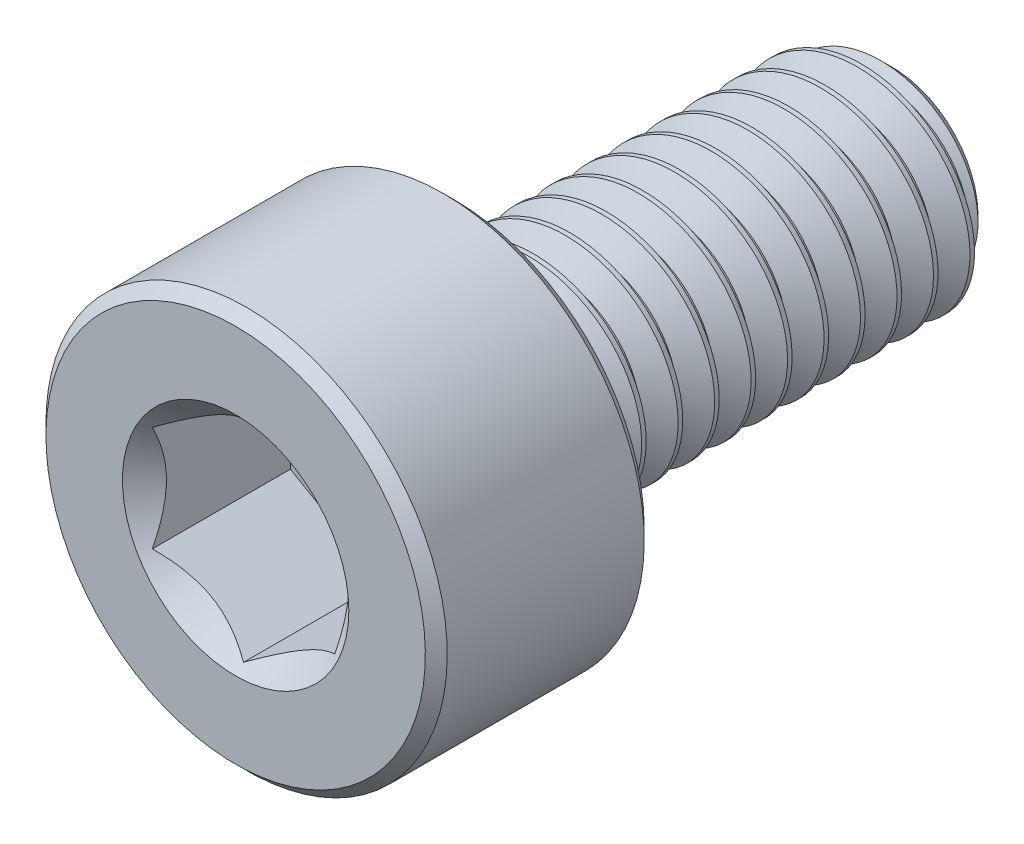
SolidWorks part; units mm, degrees
ref_plane "Front Plane" through (0, 0, 0) normal (0, 0, 1) x (1, 0, 0)
ref_plane "Top Plane" through (0, 0, 0) normal (0, 1, 0) x (1, 0, 0)
ref_plane "Right Plane" through (0, 0, 0) normal (1, 0, 0) x (0, 0, -1)
sketch "Sketch1" plane through (0, 0, 0) normal (1, 0, 0) x (0, 0, -1)
  line L0 (-4.5, 0) -> (4.5, 0) construction
  line L1 (4.5, 0) -> (4.5, 1.1752) construction
  line L2 (4.5, 1.1752) -> (4.1752, 1.5) construction
  line L3 (4.1752, 1.5) -> (4.125, 1.5) construction
  line L4 (4.125, 1.5) -> (-1.5, 1.5) construction
  line L5 (-1.5, 1.5) -> (-1.5, 2.75) construction
  line L6 (-1.5, 2.75) -> (-4.5, 2.75) construction
  line L7 (-4.5, 2.75) -> (-4.5, 0) construction
  line L8 (4.5, 1.1752) -> (4.5, 1.5) construction
  line L9 (4.4687, 1.5541) -> (4.7187, 1.1211) construction
  line L10 (4.7187, 1.1211) -> (4.9687, 1.5541) construction
  line L11 (4.9687, 1.5541) -> (4.4687, 1.5541) construction
  line L12 (4.7187, 1.5541) -> (4.7188, 1.5) construction
  line L13 (4.7187, 1.1211) -> (4.7187, 1.1752) construction
  line L14 (4.6875, 1.1752) -> (4.75, 1.1752) construction
  line L15 (4.5, 1.5) -> (4.9375, 1.5) construction
  line L16 (4.4844, 1.5271) -> (4.9531, 1.5271) construction
  line L17 (4.5, 0) -> (4.5, -1.5) construction
  line L18 (-1.65, 2.75) -> (-1.5, 2.6) construction
  line L19 (-4.35, 2.75) -> (-4.5, 2.6) construction
  line L20 (-1.5, 1.5) -> (-1.5, 0) construction
  line L21 (-1.5, 0.75) -> (0.5, 0.75) construction
  line L22 (0.5, 0.75) -> (2.5, 0.75) construction
  line L23 (2.5, 0.75) -> (4.5, 0.75) construction
  line L24 (0.5, 0.75) -> (0.5, 1.5) construction
  line L25 (0.5, 1.5) -> (0.5, 2.75) construction
  line L26 (2.5, 0.75) -> (2.5, 2.75) construction
  point P0 (-4.5, 1.25)
  point P3 (3.25, 1.5)
  point P4 (0, 0)
  point P18 (2.5, 1.5)
  point P22 (4.7187, 1.1752)
  point P24 (4.125, 1.5)
  point P25 (4.7188, 1.5)
  point P28 (4.7188, 1.5271)
  point P29 (3.25, -1.5)
  point P30 (0.5, 1.5)
  point P31 (-3, 2.75)
  point P37 (-2.025, 2.75)
  point P38 (-4.275, 2.75)
  point P45 (0.5, 0.75)
  point P46 (2.5, 0.75)
  dimension "D2" = 0.0625
  dimension "D7" = 0.15
  dimension "D8" = 0.15
  dimension "D9" = 0.15
  dimension "D10" = 0.075
  dimension "D11" = 0.375
  dimension "Drive Size" = 2.5
  dimension "Head Diameter" = 5.5
  dimension "Head Height" = 3
  dimension "Thread Pitch" = 0.5
  dimension "Thread Dia" = 3
  dimension "Length" = 6
  dimension "D12" = 0.375
  dimension "D4" = 1.25
  dimension "D3" = 45
sketch "Sketch2" plane through (0, 0, 0) normal (1, 0, 0) x (0, 0, -1)
  line L0 (-4.5, 0) -> (-4.5, 2.6)
  line L1 (-4.35, 2.75) -> (-1.65, 2.75)
  line L2 (-1.5, 2.6) -> (-1.5, 1.65)
  line L4 (4.1752, 1.5) -> (4.5, 1.1752)
  line L5 (4.5, 1.1752) -> (4.5, 0)
  line L6 (-1.5, 2.75) -> (-4.5, 2.75) construction
  line L7 (4.5, 0) -> (-4.5, 0)
  line L8 (-4.35, 2.75) -> (-4.5, 2.6) construction
  line L10 (-4.35, 2.75) -> (-4.5, 2.6)
  line L14 (-1.65, 2.75) -> (-1.5, 2.6) construction
  line L16 (-1.65, 2.75) -> (-1.5, 2.6)
  line L17 (-1.5, 1.5) -> (-1.5, 2.75) construction
  line L19 (-1.35, 1.5) -> (4.1752, 1.5)
  line L20 (4.125, 1.5) -> (-1.5, 1.5) construction
  arc A1 (-1.5, 1.65) -> (-1.35, 1.5) centre (-1.35, 1.65) ccw
  dimension "D3" = 0.15
revolve "Revolve1" add sketch "Sketch2" angle 360 about L7
sketch "Sketch3" plane through (0, 0, 4.5) normal (0, 0, 1) x (1, 0, 0)
  line L1 (1.25, -0.7217) -> (1.25, 0.7217)
  line L2 (1.25, 0.7217) -> (0, 1.4434)
  line L3 (0, 1.4434) -> (-1.25, 0.7217)
  line L4 (-1.25, 0.7217) -> (-1.25, -0.7217)
  line L5 (-1.25, -0.7217) -> (0, -1.4434)
  line L6 (0, -1.4434) -> (1.25, -0.7217)
  circle A0 centre (0, 0) radius 1.25 construction
  circle A1 centre (0, 0) radius 2.75 construction
  circle A2 centre (0, 0) radius 2.75 construction
  circle A3 centre (0, 0) radius 1.4434 construction
  point P13 (0, 0)
  dimension "D1" = 2.8868
extrude "Cut-Extrude1" cut sketch "Sketch3" against normal offset from surface (2 mm away) 1 up to face at (0, 2.6, 1.5)
sketch "Sketch4" plane through (0, 0, 4.5) normal (0, 0, 1) x (1, 0, 0)
  circle A0 centre (0, 0) radius 1.5516
  dimension "D1" = 3.1033
extrude "Cut-Extrude2" cut sketch "Sketch4" against normal up to vertex (1.5 mm away) draft 45 up to point (0, 2.75, 3)
sketch "Sketch11" plane through (0, 0, 0) normal (1, 0, 0) x (0, 0, -1)
  line L0 (-4.5, 0) -> (4.5, 0) construction
  line L1 (-4.5, 0) -> (4.5, 0) construction
  line L2 (-0.375, 0) -> (-0.375, 1.5) construction
  line L3 (4.125, 1.5) -> (-1.5, 1.5) construction
  line L4 (3.375, 0) -> (3.375, 1.5) construction
  line L6 (4.5, 1.1752) -> (4.5, 1.5) construction
  point P2 (-0.375, 0)
  point P3 (3.375, 0)
  dimension "D1" = 1.125
  dimension "D2" = 1.125
sketch "Sketch6" plane through (0, 0, -4.5) normal (0, 0, -1) x (-1, 0, 0)
  circle A0 centre (0, 0) radius 1.5
curve "Helix/Spiral1" pitch 0.5 height 6.5 radius 1.5 centre (0, 0, -4.5) axis (0, 0, 1) start towards (0, 1, 0)
sketch "Sketch10" plane through (0, 0, 0) normal (1, 0, 0) x (0, 0, -1)
  line L0 (-1.35, -2.75) -> (-1.35, 2.75)
  line L5 (-4.5, 0) -> (4.5, 0) construction
  line L6 (-1.35, 1.5) -> (-1.35, -1.5) construction
  point P3 (-1.35, 0)
split "Split1" trim tools "Sketch10" bodies to split 106 resulting bodies 114 115
sketch "Sketch7" plane through (0, 0, 0) normal (1, 0, 0) x (0, 0, -1)
  line L0 (4.4844, 1.5271) -> (4.9531, 1.5271)
  line L1 (4.9531, 1.5271) -> (4.75, 1.1752)
  line L2 (4.75, 1.1752) -> (4.6875, 1.1752)
  line L3 (4.6875, 1.1752) -> (4.4844, 1.5271)
sweep "Cut-Sweep1" cut profiles "Sketch7" path "Helix/Spiral1" align with end faces yes
sketch "Sketch8" plane through (0, 0, 0) normal (1, 0, 0) x (0, 0, -1)
  line L0 (-1.5, 0) -> (-1.5, 1.5)
  line L1 (-1.35, -1.5) -> (-1.35, 1.5) construction
  line L2 (-1.5, 1.5) -> (-1.35, 1.5)
  line L4 (-1.35, 1.5) -> (-0.484, 0)
  line L5 (-0.484, 0) -> (-1.5, 0)
  line L6 (4.125, 1.5) -> (-1.5, 1.5) construction
  line L7 (-4.5, 0) -> (4.5, 0) construction
  dimension "D1" = 60
revolve "Revolve2" add sketch "Sketch8" angle 360 about L5
equation "\"D2@Sketch1\" = \"Thread Pitch@Sketch1\" / 8"
equation "\"D4@Helix/Spiral1\" = \"Thread Pitch@Sketch1\""
equation "\"D7@Sketch1\" = \"Head Height@Sketch1\" * .05"
equation "\"D8@Sketch1\"=\"D7@Sketch1\""
equation "\"D9@Sketch1\"=\"D7@Sketch1\""
equation "\"D10@Sketch1\"=\"D7@Sketch1\"/2"
equation "\"D11@Sketch1\"=\"D10@Sketch1\"*5"
equation "\"D4@Sketch1\"=\"Thread Pitch@Sketch1\"*2.5"
equation "\"D12@Sketch1\"=\"Thread Pitch@Sketch1\"*.75"
equation "\"D3@Helix/Spiral1\"=\"Length@Sketch1\"+\"Thread Pitch@Sketch1\""
equation "\"D3@Sketch2\"=\"Thread Dia@Sketch1\"*0.05"
equation "\"D1@Sketch11\"=\"Length@Sketch1\"*0.1875"
equation "\"D2@Sketch11\"=\"D1@Sketch11\""
equation "\"D1@Sketch4\"=\"D1@Sketch3\"*1.075"
